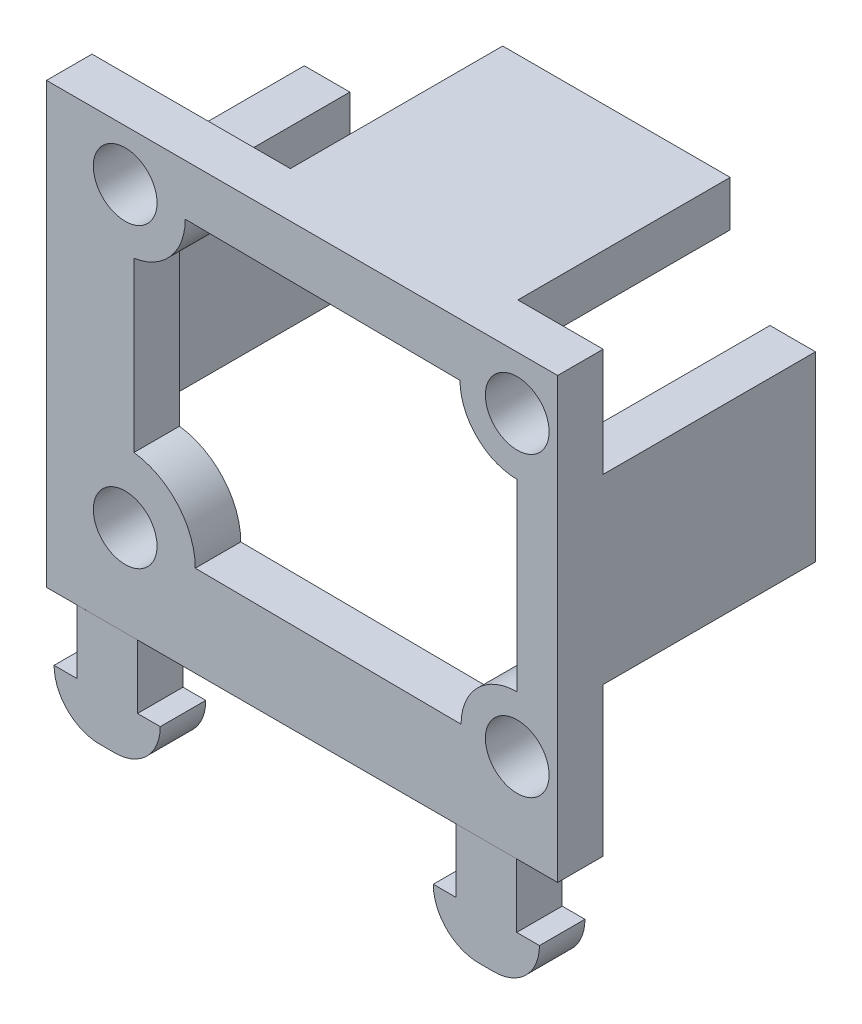
SolidWorks part; units mm, degrees
ref_plane "Спереди" through (0, 0, 0) normal (0, 0, 1) x (1, 0, 0)
ref_plane "Сверху" through (0, 0, 0) normal (0, 1, 0) x (1, 0, 0)
ref_plane "Справа" through (0, 0, 0) normal (1, 0, 0) x (0, 0, -1)
sketch "Эскиз2" plane through (0, 0, 0) normal (0, 0, 1) x (1, 0, 0)
  line L0 (-5.766, 0) -> (-5.766, -2.25)
  line L1 (27.934, 26.7) -> (-5.766, 26.7)
  line L2 (27.934, 26.7) -> (27.934, 0)
  line L3 (52.9702, -2.25) -> (-196.0298, -2.25) construction
  line L4 (-5.766, 26.7) -> (-5.766, 0)
  line L5 (-5.766, -2.25) -> (27.934, -2.25)
  line L6 (27.934, -2.25) -> (27.934, 0)
  line L7 (27.934, 26.7) -> (30.9983, 26.7) construction
  line L8 (-0.5793, 23.3473) -> (-0.6155, 26.7) construction
  line L9 (-0.5793, 23.3473) -> (-5.766, 23.3473) construction
  line L10 (0, 19.4273) -> (0, 8.3348)
  line L11 (25.2685, 19.4273) -> (25.2685, 7.303)
  line L12 (4.042, 3.75) -> (21.567, 3.6015)
  line L13 (-5.766, 26.7) -> (-0.6155, 26.7) construction
  line L14 (21.4944, 23.2014) -> (3.3832, 23.3473)
  circle A0 centre (25.2685, 3.6015) radius 2.1
  circle A1 centre (25.2685, 23.2014) radius 2.1
  circle A2 centre (-0.5793, 23.3473) radius 2.1
  circle A3 centre (-0.5793, 3.75) radius 2.1
  arc A4 (25.2685, 7.303) -> (21.567, 3.6015) centre (25.2685, 3.6015) ccw
  arc A5 (21.4944, 23.2014) -> (25.2685, 19.4273) centre (25.2685, 23.2014) ccw
  arc A6 (0, 19.4273) -> (3.3832, 23.3473) centre (-0.5793, 23.3473) ccw
  arc A7 (4.042, 3.75) -> (0, 8.3348) centre (-0.5793, 3.75) ccw
  point P12 (30.9983, 21.5985)
  point P13 (30.9983, 4.9988)
  point P14 (30.9983, 1.9985)
  point P15 (30.9983, 24.5985)
  point P16 (32.4984, 3.4986)
  point P25 (5.1505, 21.4035)
  point P26 (5.1505, 24.4965)
  dimension "D1" = 26.7
  dimension "D3" = 4.2
  dimension "D4" = 4.2
  dimension "D5" = 4.2
  dimension "D6" = 4.2
  dimension "D2" = 33.7
  dimension "D7" = 3.3529
  dimension "D8" = 5.1866
extrude "Бобышка-Вытянуть1" add sketch "Эскиз2" along normal blind 2 and the other way blind 1
sketch "Эскиз4" plane through (0, 0, 2) normal (0, 0, 1) x (1, 0, 0)
  line L0 (1.6553, 21.9507) -> (24.5148, 4.4565) construction
  line L2 (4.085, 5.0737) -> (22.085, 5.0737)
  line L3 (1.085, 8.0737) -> (1.085, 18.3335)
  line L4 (4.085, 21.3335) -> (22.085, 21.3335)
  line L5 (25.085, 8.0737) -> (25.085, 18.3335)
  line L6 (1.085, 5.0737) -> (25.085, 21.3335) construction
  line L7 (1.085, 21.3335) -> (25.085, 5.0737) construction
  arc A0 (22.085, 5.0737) -> (25.085, 8.0737) centre (22.085, 8.0737) ccw
  arc A1 (4.085, 5.0737) -> (1.085, 8.0737) centre (4.085, 8.0737) cw
  arc A2 (22.085, 21.3335) -> (25.085, 18.3335) centre (22.085, 18.3335) cw
  arc A3 (1.085, 18.3335) -> (4.085, 21.3335) centre (4.085, 18.3335) cw
  point P4 (13.085, 13.2036)
  dimension "D3" = 3
  dimension "D4" = 3
  dimension "D5" = 3
  dimension "D6" = 3
  dimension "D1" = 16.2598
  dimension "D2" = 24
extrude "Вырез-Вытянуть1" [suppressed] cut sketch "Эскиз4" against normal blind 3
sketch "Эскиз10" plane through (0, 0, -1) normal (0, 0, -1) x (-1, 0, 0)
  line L0 (-27.934, 0.75) -> (-22.3105, 0.75) construction
  line L1 (-22.3105, 0.75) -> (-22.3105, 23.7) construction
  line L2 (2.766, 3.3527) -> (-7.3105, 3.3527) construction
  line L3 (-7.3105, 3.3527) -> (-7.3105, 23.7) construction
  line L9 (-27.934, 26.7) -> (5.766, 26.7) construction
  line L10 (-22.3105, 23.7) -> (-7.3105, 23.7)
  line L11 (-22.3105, 23.7) -> (-22.3105, 26.7)
  line L12 (-22.3105, 26.7) -> (-7.3105, 26.7)
  line L13 (-7.3105, 23.7) -> (-7.3105, 26.7)
  line L14 (-27.934, 0.75) -> (-27.934, 7.5529) construction
  line L15 (-27.934, 23.0985) -> (-27.934, 19.5529) construction
  line L17 (-27.934, 7.5529) -> (-24.934, 7.5529)
  line L18 (-27.934, 7.5529) -> (-27.934, 19.5529)
  line L19 (-27.934, 19.5529) -> (-24.934, 19.5529)
  line L20 (-24.934, 7.5529) -> (-24.934, 19.5529)
  line L21 (2.766, 7.5529) -> (2.766, 19.0325) construction
  line L22 (5.766, 26.7) -> (5.766, -2.25) construction
  line L23 (2.766, 7.5529) -> (5.766, 7.5529)
  line L24 (2.766, 7.5529) -> (2.766, 19.0325)
  line L25 (2.766, 19.0325) -> (5.766, 19.0325)
  line L26 (5.766, 7.5529) -> (5.766, 19.0325)
  line L27 (-27.934, -2.25) -> (-27.934, 26.7) construction
  dimension "D1" = 15
  dimension "D2" = 12
  dimension "D3" = 3
  dimension "D4" = 3
  dimension "D6" = 3
extrude "Бобышка-Вытянуть4" add sketch "Эскиз10" along normal blind 14
sketch "Эскиз11" plane through (0, -2.25, 0) normal (0, -1, 0) x (1, 0, 0)
  line L0 (-5.766, 2) -> (-3.766, 2.0001) construction
  line L1 (-1.766, 2.0001) -> (-1.766, -0.9999) construction
  line L2 (27.934, 2) -> (25.234, 2.0002) construction
  line L3 (-3.766, 2.0001) -> (0.234, 2.0001)
  line L4 (-3.766, 2.0001) -> (-3.766, -0.9999)
  line L5 (-3.766, -0.9999) -> (0.234, -0.9999)
  line L6 (0.234, 2.0001) -> (0.234, -0.9999)
  line L7 (23.234, 2.0002) -> (23.234, -0.9998) construction
  line L8 (25.234, 2.0002) -> (21.234, 2.0002)
  line L9 (25.234, 2.0002) -> (25.234, -0.9998)
  line L10 (25.234, -0.9998) -> (21.234, -0.9998)
  line L11 (21.234, 2.0002) -> (21.234, -0.9998)
  line L12 (-1.766, 0.5001) -> (23.234, 0.5002) construction
  dimension "D1" = 25
  dimension "D2" = 4
  dimension "D3" = 4
  dimension "D4" = 3
  dimension "D5" = 3
  dimension "D6" = 2
extrude "Бобышка-Вытянуть5" add sketch "Эскиз11" along normal blind 4.2
sketch "Эскиз12" plane through (0, -6.45, 0) normal (0, -1, 0) x (1, 0, 0)
  line L0 (-3.7661, 2.0001) -> (0.234, -0.9999) construction
  line L1 (21.234, 2.0002) -> (25.234, -0.9998) construction
  line L2 (-5.266, -0.9999) -> (1.734, -0.9999)
  line L3 (-5.266, -0.9999) -> (-5.266, 2.0001)
  line L4 (-5.266, 2.0001) -> (1.734, 2.0001)
  line L5 (1.734, -0.9999) -> (1.734, 2.0001)
  line L6 (-5.266, -0.9999) -> (1.734, 2.0001) construction
  line L7 (-5.266, 2.0001) -> (1.734, -0.9999) construction
  line L8 (-3.766, 2) -> (0.234, -0.9999) construction
  line L9 (19.734, -0.9998) -> (26.734, -0.9998)
  line L10 (19.734, -0.9998) -> (19.734, 2.0002)
  line L11 (19.734, 2.0002) -> (26.734, 2.0002)
  line L12 (26.734, -0.9998) -> (26.734, 2.0002)
  line L13 (19.734, -0.9998) -> (26.734, 2.0002) construction
  line L14 (19.734, 2.0002) -> (26.734, -0.9998) construction
  line L15 (-3.766, -0.9999) -> (0.234, -0.9999) construction
  point P4 (-1.766, 0.5001)
  point P13 (23.234, 0.5002)
  dimension "D1" = 3
  dimension "D2" = 7
  dimension "D3" = 3
  dimension "D4" = 7
extrude "Бобышка-Вытянуть6" add sketch "Эскиз12" along normal blind 3
fillet "Скругление4" radius 3 1 edges at (-5.266, -9.45, 0.5001) type face fillet first side face at (-5.266, -7.95, 0.5001) second side face at (-1.766, -9.45, 0.5001)
fillet "Скругление5" radius 3 1 edges at (1.734, -9.45, 0.5001) type face fillet first side face at (1.734, -7.95, 0.5001) second side face at (-0.266, -9.45, 0.5001)
fillet "Скругление6" radius 3 1 edges at (26.734, -9.45, 0.5002) type face fillet first side face at (23.234, -9.45, 0.5002) second side face at (26.734, -7.95, 0.5002)
fillet "Скругление7" radius 3 1 edges at (19.734, -9.45, 0.5002) type face fillet first side face at (21.734, -9.45, 0.5002) second side face at (19.734, -7.95, 0.5002)
